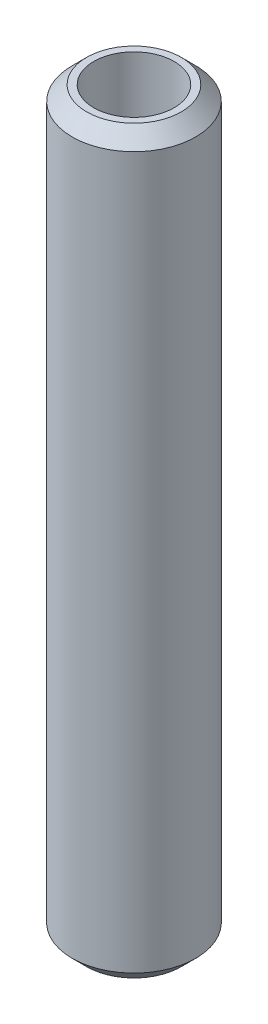
SolidWorks part; units mm, degrees
ref_plane "Front Plane" through (0, 0, 0) normal (0, 0, 1) x (1, 0, 0)
ref_plane "Top Plane" through (0, 0, 0) normal (0, 1, 0) x (1, 0, 0)
ref_plane "Right Plane" through (0, 0, 0) normal (1, 0, 0) x (0, 0, -1)
sketch "Sketch1" plane through (0, 0, 0) normal (0, 1, 0) x (1, 0, 0)
  circle A0 centre (0, 0) radius 7.5
  dimension "SHAFT_OD" = 15
extrude "Boss-Extrude1" add sketch "Sketch1" along normal blind 89.9053
sketch "Sketch2" plane through (0, 0, 0) normal (0, 1, 0) x (1, 0, 0)
  circle A0 centre (0, 0) radius 4.8791
  dimension "BORE_D" = 9.7582
extrude "Cut-Extrude1" cut sketch "Sketch2" along normal through all
chamfer "Chamfer1" distance 1.7574 angle 45 2 edges at (0, 89.9053, 7.5) (0, 0, 7.5)
